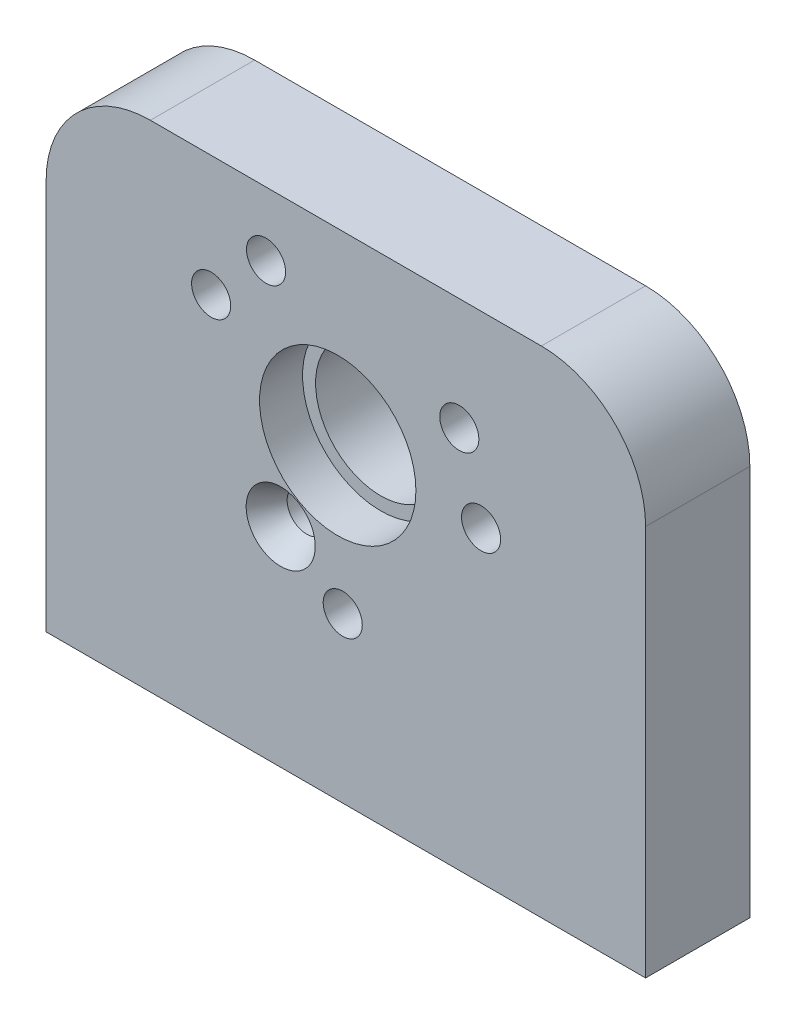
SolidWorks part; units mm, degrees
material "6061 Alloy"
ref_plane "Front Plane" through (0, 0, 0) normal (0, 0, 1) x (1, 0, 0)
ref_plane "Top Plane" through (0, 0, 0) normal (0, 1, 0) x (1, 0, 0)
ref_plane "Right Plane" through (0, 0, 0) normal (1, 0, 0) x (0, 0, -1)
ref_plane "Plane1" through (0, 0, 4.5) normal (0, 0, 1) x (1, 0, 0)
sketch "Sketch1" plane through (0, 0, 4.5) normal (0, 0, 1) x (1, 0, 0)
  line L0 (23, -18) -> (23, 20)
  line L1 (23, 20) -> (-23, 20)
  line L2 (-23, 20) -> (-23, -18)
  line L3 (-23, -18) -> (23, -18)
  dimension "D1" = 46
  dimension "D2" = 38
extrude "Boss-Extrude1" add sketch "Sketch1" against normal blind 8
ref_plane "Plane2" through (0, -2, 0) normal (0, 1, 0) x (1, 0, 0)
sketch "Sketch4" plane through (0, -2, 0) normal (0, 1, 0) x (1, 0, 0)
  line L0 (-1, 6.5) -> (-5, 6.5)
  line L1 (-5, 6.5) -> (-5, 3.5)
  line L2 (-5, 3.5) -> (-1, 3.5)
  line L3 (-1, 3.5) -> (-1, 6.5)
  line L4 (-5, 6.5) -> (-5, 3.5) construction
  dimension "D1" = 3
  dimension "D2" = 4
  dimension "D3" = 6.5
revolve "Revolve1" [suppressed] add sketch "Sketch4" angle 360 about L4
hole_wizard "Ø2.5 (2.5) Diameter Hole2" positions "Sketch6" profile "Sketch5" hole size "Ø2.5" standard "ANSI Metric"
sketch "Sketch6" plane through (0, -18, 0) normal (0, -1, 0) x (-1, 0, 0)
  line L0 (23, -4.5) -> (-23, -4.5) construction
  point P0 (0, -0.5)
  dimension "D1" = 4
sketch "Sketch5" plane through (0, -18, 0.5) normal (1, 0, 0) x (0, 0, -1)
  line L0 (0, 0) -> (0, 8.7511)
  line L1 (0, 8.7511) -> (1.25, 8)
  line L2 (1.25, 8) -> (1.25, 0)
  line L5 (1.25, 0) -> (0, 0)
  line L10 (0, 8.7511) -> (-1.25, 8) construction
  line L11 (0, -6.35) -> (0, 107.95) construction
  dimension "Hole Dia." = 2.5
  dimension "Hole Depth" = 8
  dimension "Drill Angle" = 118
hole_wizard "Ø2.5 (2.5) Diameter Hole1" positions "Sketch8" profile "Sketch7" hole size "Ø2.5" standard "ANSI Metric"
sketch "Sketch8" plane through (0, -18, 0) normal (0, -1, 0) x (-1, 0, 0)
  line L0 (23, -4.5) -> (-23, -4.5) construction
  point P0 (19, -0.5)
  point P1 (-19, -0.5)
  dimension "D1" = 4
sketch "Sketch7" plane through (-19, -18, 0.5) normal (1, 0, 0) x (0, 0, -1)
  line L0 (0, 0) -> (0, 8.7511)
  line L1 (0, 8.7511) -> (1.25, 8)
  line L2 (1.25, 8) -> (1.25, 0)
  line L5 (1.25, 0) -> (0, 0)
  line L10 (0, 8.7511) -> (-1.25, 8) construction
  line L11 (0, -6.35) -> (0, 107.95) construction
  dimension "Hole Dia." = 2.5
  dimension "Hole Depth" = 8
  dimension "Drill Angle" = 118
hole_wizard "Ø4.2 (4.2) Diameter Hole1" [suppressed] positions "Sketch14" profile "Sketch13" hole size "Ø4.2" standard "ANSI Metric"
sketch "Sketch14" [suppressed] plane through (0, 0, -6.5) normal (0, 0, -1) x (-1, 0, 0)
  point P0 (5, -2)
sketch "Sketch13" plane through (-5, -2, -6.5) normal (1, 0, 0) x (0, 1, 0)
  line L0 (0, 0) -> (0, 7)
  line L1 (0, 7) -> (2.1, 7)
  line L2 (2.1, 7) -> (2.1, 0)
  line L5 (2.1, 0) -> (0, 0)
  line L10 (0, 7) -> (-2.1, 7) construction
  line L11 (0, -6.35) -> (0, 107.95) construction
  dimension "Hole Dia." = 4.2
  dimension "Hole Depth" = 7
  dimension "Drill Angle" = 180
fillet "Fillet2" radius 8 2 edges at (23, 20, 0.5) (-23, 20, 0.5) tangent propagation no
sketch "Sketch16" plane through (0, 0, -3.5) normal (0, 0, -1) x (-1, 0, 0)
  line L0 (23, -18) -> (-23, -18) construction
  line L1 (2.5, -4.5) -> (7.5, -4.5)
  line L2 (2.5, -4.5) -> (2.5, 0.5)
  line L3 (2.5, 0.5) -> (7.5, 0.5)
  line L4 (7.5, -4.5) -> (7.5, 0.5)
  line L5 (2.5, -4.5) -> (7.5, 0.5) construction
  line L6 (2.5, 0.5) -> (7.5, -4.5) construction
  line L9 (23, 12) -> (23, -18) construction
  point P0 (5, -2)
  dimension "D1" = 16
  dimension "D2" = 18
  dimension "D3" = 5
extrude "Cut-Extrude1" cut sketch "Sketch16" against normal blind 4.5
hole_wizard "CSK for M3 SFHCS1" positions "3DSketch1" profile "Sketch17" countersink size "M3" standard "ANSI Metric"
sketch3d "3DSketch1"
  line L0 (-23, -18, 4.5) -> (23, -18, 4.5) construction
  line L1 (-23, 12, 4.5) -> (-23, -18, 4.5) construction
  point P0 (-5, -2, 4.5)
  dimension "D1" = 16
  dimension "D2" = 18
sketch "Sketch17" plane through (-5, -2, 4.5) normal (1, 0, 0) x (0, -1, 0)
  line L0 (0, 0) -> (0, 10.4013)
  line L1 (0, 10.4013) -> (1.5, 9.5)
  line L2 (1.5, 9.5) -> (1.5, 1.9919)
  line L3 (1.5, 1.9919) -> (2.65, 0)
  line L5 (2.65, 0) -> (0, 0)
  line L6 (-1.5, 1.9919) -> (-2.65, 0) construction
  line L10 (0, 10.4013) -> (-1.5, 9.5) construction
  line L11 (0, -6.35) -> (0, 107.95) construction
  dimension "Hole Dia." = 3
  dimension "Hole Depth" = 9.5
  dimension "Near C'Sink Dia." = 5.3
  dimension "Near C'Sink Angle" = 60
  dimension "Drill Angle" = 118
hole_wizard "Hole1" positions "Sketch12" profile "Sketch11" legacy end condition through all
sketch "Sketch12" plane through (0, 0, 4.5) normal (0, 0, 1) x (1, 0, 0)
  line L0 (-5, -2) -> (-0.625, 5.5777) construction
  line L1 (-0.625, 5.5777) -> (-0.625, -18) construction
  line L2 (-23, -18) -> (23, -18) construction
  point P0 (-0.625, 5.5777)
  dimension "D1" = 8.75
  dimension "D2" = 30
sketch "Sketch11" plane through (-0.625, 5.5777, 4.5) normal (1, 0, 0) x (0, -1, 0)
  line L0 (0, 0) -> (0, 8)
  line L1 (0, 8) -> (5, 8)
  line L2 (5, 8) -> (5, 3.3)
  line L3 (5, 3.3) -> (6, 3.3)
  line L4 (6, 3.3) -> (6, 0)
  line L5 (6, 0) -> (0, 0)
  line L6 (0, 110) -> (0, -10) construction
  dimension "Diameter" = 10
  dimension "Depth" = 8
  dimension "C-Bore Diameter" = 12
  dimension "C-Bore Depth" = 3.3
hole_wizard "CSK for M3 SFHCS2" positions "Sketch10" profile "Sketch9" countersink size "M3" standard "ANSI Metric"
sketch "Sketch10" plane through (0, 0, -3.5) normal (0, 0, -1) x (-1, 0, 0)
  line L1 (10.3374, 10.7419) -> (-8.7035, 11.4068) construction
  line L2 (-8.7035, 11.4068) -> (0.2411, -5.4156) construction
  line L3 (0.2411, -5.4156) -> (10.3374, 10.7419) construction
  line L4 (0.625, 5.5777) -> (0.2411, -5.4156) construction
  line L7 (0.625, 5.5777) -> (0.625, -18) construction
  line L8 (23, -18) -> (-23, -18) construction
  circle A0 centre (0.625, 5.5777) radius 5.5 construction
  point P30 (-8.7035, 11.4068)
  point P33 (10.3374, 10.7419)
  point P36 (0.2411, -5.4156)
  dimension "D1" = 2
sketch "Sketch9" plane through (8.7035, 11.4068, -3.5) normal (1, 0, 0) x (0, 1, 0)
  line L0 (0, 0) -> (0, 10.4013)
  line L1 (0, 10.4013) -> (1.5, 9.5)
  line L2 (1.5, 9.5) -> (1.5, 2.0785)
  line L3 (1.5, 2.0785) -> (2.7, 0)
  line L5 (2.7, 0) -> (0, 0)
  line L6 (-1.5, 2.0785) -> (-2.7, 0) construction
  line L10 (0, 10.4013) -> (-1.5, 9.5) construction
  line L11 (0, -6.35) -> (0, 107.95) construction
  dimension "Hole Dia." = 3
  dimension "Hole Depth" = 9.5
  dimension "Near C'Sink Dia." = 5.4
  dimension "Near C'Sink Angle" = 60
  dimension "Drill Angle" = 118
fillet "Fillet3" radius 1 4 edges at (-2.5, -4.5, -1.0226) (-7.5, -4.5, -1.25) (-7.5, 0.5, -1.25) (-2.5, 0.5, -1.25)
sketch "Sketch18" plane through (0, 0, -3.5) normal (0, 0, -1) x (-1, 0, 0)
  line L0 (0.625, 20) -> (0.625, -18) construction
  line L1 (6.125, 15.104) -> (-10.375, 5.5777) construction
  line L2 (-10.375, 5.5777) -> (6.125, -3.9486) construction
  line L3 (6.125, -3.9486) -> (6.125, 15.104) construction
  line L4 (-15, 20) -> (15, 20) construction
  line L5 (23, -18) -> (-23, -18) construction
  line L6 (0.625, 5.5777) -> (6.125, -3.9486) construction
  circle A0 centre (0.625, 5.5777) radius 5.5 construction
  dimension "D1" = 11
  dimension "D2" = 30
hole_wizard "CSK for M3 SFHCS3" positions "3DSketch2" profile "Sketch19" countersink size "M3" standard "ANSI Metric"
sketch3d "3DSketch2"
  point P0 (-6.125, 15.104, -3.5)
  point P3 (10.375, 5.5777, -3.5)
sketch "Sketch19" plane through (-6.125, 15.104, -3.5) normal (1, 0, 0) x (0, 1, 0)
  line L0 (0, 0) -> (0, 10.4013)
  line L1 (0, 10.4013) -> (1.5, 9.5)
  line L2 (1.5, 9.5) -> (1.5, 2.0785)
  line L3 (1.5, 2.0785) -> (2.7, 0)
  line L5 (2.7, 0) -> (0, 0)
  line L6 (-1.5, 2.0785) -> (-2.7, 0) construction
  line L10 (0, 10.4013) -> (-1.5, 9.5) construction
  line L11 (0, -6.35) -> (0, 107.95) construction
  dimension "Hole Dia." = 3
  dimension "Hole Depth" = 9.5
  dimension "Near C'Sink Dia." = 5.4
  dimension "Near C'Sink Angle" = 60
  dimension "Drill Angle" = 118
